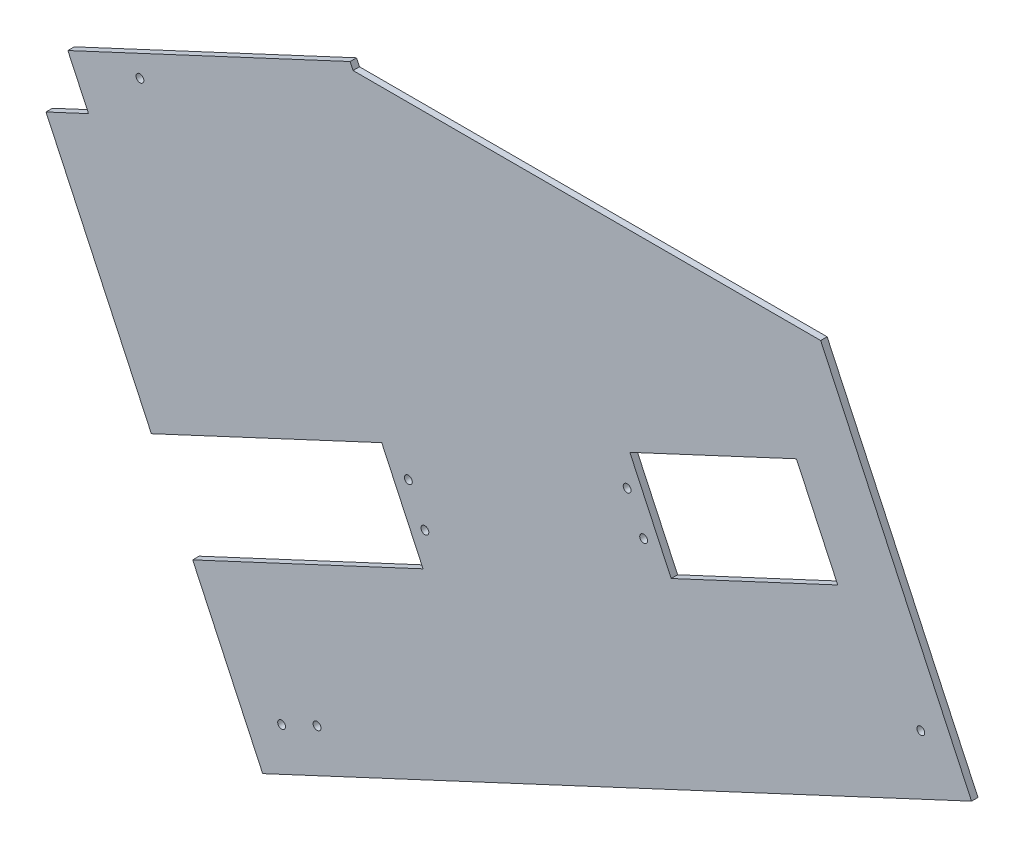
SolidWorks part; units mm, degrees
material "Balsa"
ref_plane "Front Plane" through (0, 0, 0) normal (0, 0, 1) x (1, 0, 0)
ref_plane "Top Plane" through (0, 0, 0) normal (0, 1, 0) x (1, 0, 0)
ref_plane "Right Plane" through (0, 0, 0) normal (1, 0, 0) x (0, 0, -1)
sketch "Sketch1" plane through (0, 0, 0) normal (0, 0, 1) x (1, 0, 0)
  line L0 (321.5462, 12.6346) -> (82.3833, 12.6346)
  line L1 (82.3833, 12.6346) -> (80.8781, 15.8625)
  line L2 (80.8781, 15.8625) -> (-63.4467, -51.4373)
  line L3 (-63.4467, -51.4373) -> (57.9293, -311.7289) construction
  line L4 (57.9293, -311.7289) -> (398.701, -152.8244)
  line L5 (271.5352, 119.8836) -> (277.3251, 107.4672) construction
  line L6 (190.5834, 136.311) -> (-12.0446, 41.824) construction
  line L7 (-63.4467, -51.4373) -> (255.5737, 97.3243) construction
  line L8 (398.701, -152.8244) -> (321.5462, 12.6346)
  line L9 (57.9293, -311.7289) -> (36.1779, -321.8717)
  line L10 (36.1779, -321.8717) -> (-74.6326, -84.2378)
  line L12 (-74.6326, -84.2378) -> (-52.8812, -74.095)
  line L13 (-90.9879, -49.1637) -> (-85.1981, -61.5801) construction
  line L14 (-52.8812, -74.095) -> (-63.4467, -51.4373)
  line L15 (73.956, 12.6346) -> (314.6178, 12.6346) construction
  line L16 (80.8781, 15.8625) -> (82.3833, 12.6346) construction
  circle A0 centre (162.7613, -40.6644) radius 32.5 construction
  circle A1 centre (336.0773, -108.8767) radius 32.5 construction
  circle A2 centre (90.1802, -40.6644) radius 32.5 construction
  circle A3 centre (232.5481, -40.6644) radius 32.5 construction
  circle A4 centre (207.2768, 100.5118) radius 39.5 construction
  arc A5 (-3.3339, 41.4724) -> (-17.3744, 34.9252) centre (-8.0297, 33.2141) ccw construction
  circle A6 centre (304.5287, -40.6644) radius 32.5 construction
  circle A7 centre (254.9584, -108.8767) radius 32.5 construction
  circle A8 centre (179.3206, -108.8767) radius 32.5 construction
  circle A9 centre (101.4264, -108.8767) radius 32.5 construction
  circle A10 centre (270.383, -163.8108) radius 32.5 construction
  circle A11 centre (372.7594, -134.5783) radius 2
  point P49 (81.6307, 14.2486)
  dimension "D2" = 65
  dimension "D3" = 65
  dimension "D5" = 4
  dimension "D1" = 350
  dimension "D4" = 25
  dimension "24.5/2" = 15.8
  dimension "D6" = 27.5
extrude "Boss-Extrude1" add sketch "Sketch1" along normal up to surface (3.3 mm away)
sketch "Sketch2" plane through (0, 0, 3.3) normal (0, 0, 1) x (1, 0, 0)
  circle A0 centre (105.1447, 16.1444) radius 2
  circle A1 centre (-26.5934, -45.2861) radius 2
  circle A2 centre (-26.5934, -45.2861) radius 2 construction
  circle A3 centre (105.1447, 16.1444) radius 2 construction
extrude "Cut-Extrude1" cut sketch "Sketch2" against normal through all
sketch "Sketch3" plane through (0, 0, 3.3) normal (0, 0, 1) x (1, 0, 0)
  line L2 (398.701, -152.8244) -> (36.1779, -321.8717) construction
  line L3 (36.1779, -321.8717) -> (-74.6326, -84.2378) construction
  circle A0 centre (45.8517, -295.2932) radius 2
  circle A1 centre (63.9779, -286.8408) radius 2
  dimension "D1" = 4
  dimension "D2" = 4
  dimension "D3" = 20
  dimension "D5" = 20
  dimension "D6" = 20
  dimension "D4" = 20
extrude "Cut-Extrude2" cut sketch "Sketch3" against normal blind 4
sketch "Sketch4" plane through (0, 0, 3.3) normal (0, 0, 1) x (1, 0, 0)
  line L0 (330.2782, -91.2744) -> (309.1473, -45.959)
  line L1 (309.1473, -45.959) -> (223.9543, -85.6851)
  line L2 (223.9543, -85.6851) -> (245.0853, -131.0005)
  line L3 (245.0853, -131.0005) -> (330.2782, -91.2744)
  line L4 (309.1473, -45.959) -> (223.9543, -85.6851) construction
  line L5 (245.0853, -131.0005) -> (330.2782, -91.2744) construction
  line L6 (330.2782, -91.2744) -> (309.1473, -45.959) construction
  line L7 (118.2022, -190.1671) -> (97.0712, -144.8517)
  line L8 (97.0712, -144.8517) -> (-20.7488, -199.7921)
  line L9 (-20.7488, -199.7921) -> (0.3821, -245.1075)
  line L10 (0.3821, -245.1075) -> (118.2022, -190.1671)
  line L11 (118.2022, -190.1671) -> (0.3821, -245.1075) construction
  line L12 (-20.7488, -199.7921) -> (97.0712, -144.8517) construction
  line L13 (97.0712, -144.8517) -> (118.2022, -190.1671) construction
extrude "Cut-Extrude3" cut sketch "Sketch4" against normal blind 10
sketch "Sketch5" plane through (0, 0, 3.3) normal (0, 0, 1) x (1, 0, 0)
  circle A0 centre (231.009, -120.4069) radius 2
  circle A1 centre (222.5566, -102.2807) radius 2
  circle A2 centre (119.135, -172.5746) radius 2
  circle A3 centre (110.6826, -154.4484) radius 2
  circle A4 centre (119.135, -172.5746) radius 2 construction
  circle A7 centre (110.6826, -154.4484) radius 2 construction
  circle A8 centre (222.5566, -102.2807) radius 2 construction
  circle A9 centre (231.009, -120.4069) radius 2 construction
extrude "Cut-Extrude4" cut sketch "Sketch5" against normal blind 10
